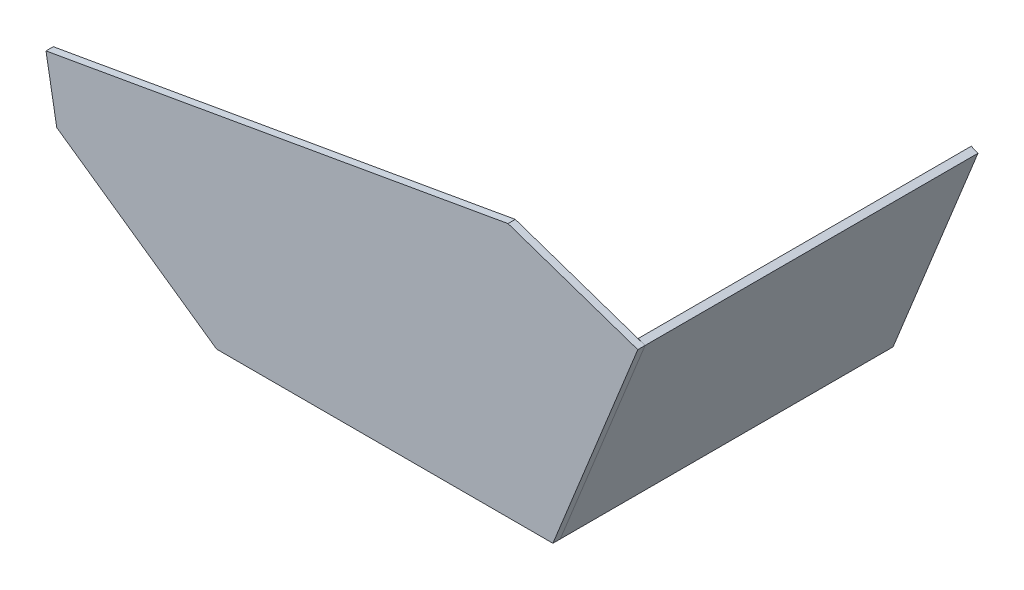
SolidWorks part; units mm, degrees
material "Melamine"
ref_plane "Front Plane" through (0, 0, 0) normal (0, 0, 1) x (1, 0, 0)
ref_plane "Top Plane" through (0, 0, 0) normal (0, 1, 0) x (1, 0, 0)
ref_plane "Right Plane" through (0, 0, 0) normal (1, 0, 0) x (0, 0, -1)
ref_axis "Axis1" through (0, 0, -14.8175) along (0, 0, 1)
sketch "Sketch1" plane through (0, 0, 0) normal (0, 0, 1) x (1, 0, 0)
  line L0 (-137.5, 0) -> (137.5, 0) construction
  line L1 (-137.5, 0) -> (-301.3304, 114.7153) construction
  line L4 (-148.5709, 0) -> (-304.9726, 109.5137) construction
  line L5 (-304.9726, 109.5137) -> (-301.3304, 114.7153) construction
  line L11 (137.5, 0) -> (144.3487, 0)
  line L12 (137.5, 0) -> (212.4213, 185.4368) construction
  line L14 (144.3487, 0) -> (218.3089, 183.058)
  line L15 (218.3089, 183.058) -> (212.4213, 185.4368)
  line L16 (212.4213, 185.4368) -> (137.5, 0)
  line L17 (-137.5, 0) -> (-148.5709, 0) construction
  point P4 (0, 0)
  dimension "D1" = 35
  dimension "D2" = 275
  dimension "D4" = 200
  dimension "D6" = 6.35
  dimension "D7" = 68
  dimension "D8" = 200
  dimension "D9" = 6.35
extrude "Boss-Extrude1" add sketch "Sketch1" along normal blind 290
sketch "Sketch2" plane through (0, 0, 290) normal (0, 0, 1) x (1, 0, 0)
  line L1 (-297.2025, 150.6805) -> (105.2664, 221.6466)
  line L3 (144.3487, 0) -> (-148.5709, 0)
  line L4 (-148.5709, 0) -> (-287.8267, 97.508) construction
  line L5 (144.3487, 0) -> (218.3089, 183.058)
  line L7 (-287.8267, 97.508) -> (-297.2025, 150.6805)
  line L8 (-287.8267, 97.508) -> (-284.1845, 102.7096) construction
  line L9 (218.3089, 183.058) -> (105.2664, 221.6466)
  line L10 (144.3487, 0) -> (105.2664, 221.6466) construction
  line L11 (-287.8267, 97.508) -> (-148.5709, 0)
  line L13 (-148.5709, 0) -> (-137.5, 0) construction
  line L14 (-287.8267, 97.508) -> (-148.5709, 0) construction
  line L15 (-284.1845, 102.7096) -> (-137.5, 0) construction
  dimension "D1" = 10
  dimension "D2" = 200
  dimension "D3" = 6.35
  dimension "D4" = 35
  dimension "D5" = 170
  dimension "D6" = 275
extrude "Boss-Extrude2" add sketch "Sketch2" along normal blind 6.35 separate body
ref_plane "Plane1" through (0, 0, 0) normal (0.9848, 0.1736, 0) x (0, 0, 1)
